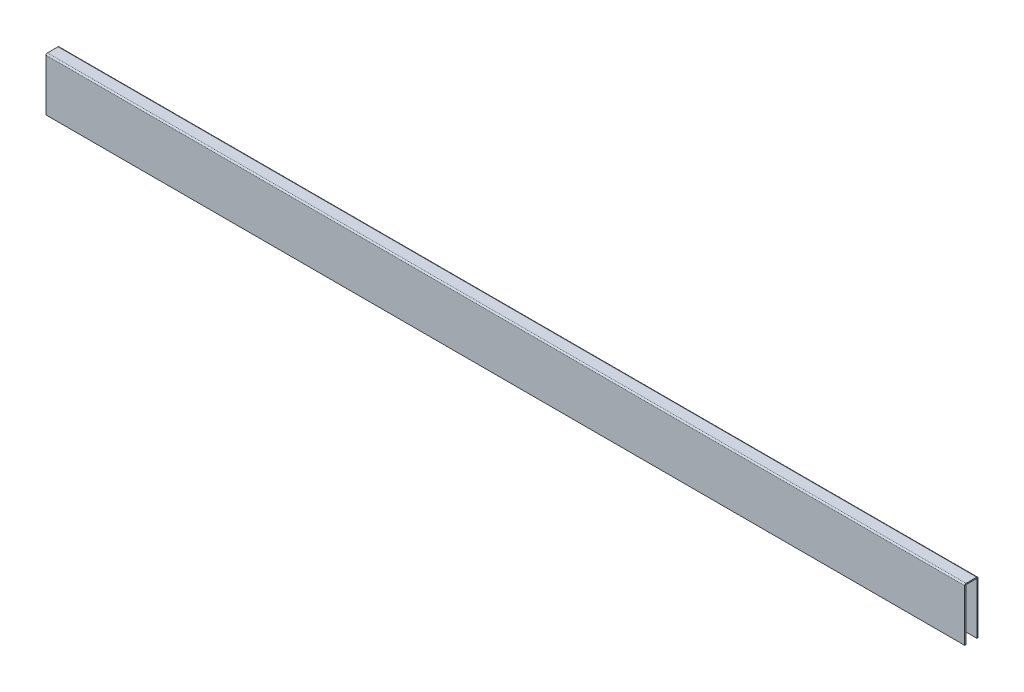
SolidWorks part; units mm, degrees
note: '?' marks a value the reader was unsure of. The reader was unsure of these and kept them because the rebuilt part matched: bend radius of "BaseBend1", "BaseBend2".
material "NEOPRENE"
ref_plane "Front Plane" through (0, 0, 0) normal (0, 0, 1) x (1, 0, 0)
ref_plane "Top Plane" through (0, 0, 0) normal (0, 1, 0) x (1, 0, 0)
ref_plane "Right Plane" through (0, 0, 0) normal (1, 0, 0) x (0, 0, -1)
ref_axis "Axis1" through (0, 0, 0) along (0, 1, 0)?
sketch "Sketch1" plane through (0, 0, 0) normal (1, 0, 0) x (0, 0, -1)
  line L1 (-0.6096, 0) -> (0.6096, 0)
  line L2 (0.6096, 0) -> (0.6096, -5.7404)
  line L9 (-0.6096, 0) -> (-0.6096, -5.7404)
  dimension "D1" = 5.7404
  dimension "D3" = 1.2192
base flange "Base-Flange1" sketch "Sketch1" end condition mid plane depth 101.6 reverse direction no thickness 0.127 reverse thickness direction no bend radius 0.0254
bend "BaseBend1" bend radius 0.0254 bend angle 90 parameters "D5"=1
bend "BaseBend2" bend radius 0.0254 bend angle 90 parameters "D5"=2
sketch "Bend-Lines1" plane through (0, 0, 0) normal (0, 1, 0) x (1, 0, 0)
sketch "Bounding-Box1" plane through (0, 0, 0) normal (0, 1, 0) x (1, 0, 0)
sheet metal parameters "Sheet-Metal2" thickness 0.127 parameters "D1"=0.0254
flat pattern "Flat-Pattern2" [suppressed]
sketch "Bend-Lines2" plane through (0, 0, 0) normal (0, 1, 0) x (1, 0, 0)
sketch "Bounding-Box2" [suppressed] plane through (0, 0, 0) normal (0, 1, 0) x (1, 0, 0)
bend of the flat pattern "Flatten-<BaseBend1>1"
bend of the flat pattern "Flatten-<BaseBend2>1"
